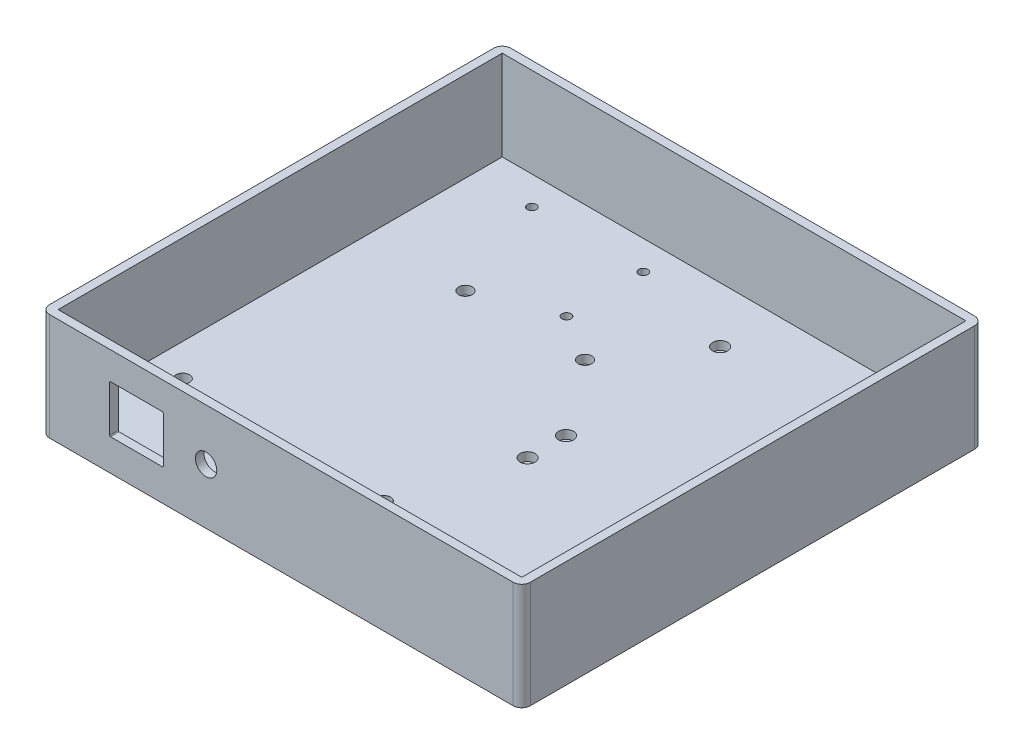
SolidWorks part; units mm, degrees
ref_plane "Front Plane" through (0, 0, 0) normal (0, 0, 1) x (1, 0, 0)
ref_plane "Top Plane" through (0, 0, 0) normal (0, 1, 0) x (1, 0, 0)
ref_plane "Right Plane" through (0, 0, 0) normal (1, 0, 0) x (0, 0, -1)
sketch "Sketch1" plane through (0, 878.6284, 0) normal (0, 1, 0) x (1, 0, 0)
  line L0 (666.5112, -1261.621) -> (666.5112, -1327.661) construction
  line L1 (661.5112, -1230.231) -> (769.8512, -1230.231)
  line L2 (661.5112, -1230.231) -> (661.5112, -1334.011)
  line L3 (661.5112, -1334.011) -> (769.8512, -1334.011)
  line L4 (769.8512, -1230.231) -> (769.8512, -1334.011)
  line L5 (666.5112, -1261.621) -> (666.5112, -1327.661)
  line L6 (666.5112, -1327.661) -> (719.8512, -1327.661) construction
  line L7 (666.5112, -1327.661) -> (719.8512, -1327.661)
  line L8 (764.8512, -1327.661) -> (764.8512, -1284.661) construction
  line L9 (708.6548, -1235.231) -> (672.3548, -1235.231) construction
  line L10 (687.3912, -1334.011) -> (676.2712, -1334.011) construction
  point P4 (643.8312, -1613.7826)
  dimension "D2" = 5
  dimension "D1" = 5
  dimension "D3" = 5
extrude "Boss-Extrude1" add sketch "Sketch1" against normal blind 4 contours L3 L4 L1 L2
sketch "Sketch2" plane through (0, 874.6284, 0) normal (0, 1, 0) x (1, 0, 0)
  line L1 (661.5112, -1230.231) -> (659.5112, -1230.231)
  line L2 (661.5112, -1230.231) -> (661.5112, -1334.011)
  line L3 (661.5112, -1334.011) -> (659.5112, -1334.011)
  line L4 (661.5112, -1230.231) -> (661.5112, -1334.011)
  line L5 (661.5112, -1334.011) -> (769.8512, -1334.011)
  line L6 (769.8512, -1334.011) -> (769.8512, -1230.231)
  line L7 (769.8512, -1230.231) -> (661.5112, -1230.231)
  line L8 (661.5112, -1230.231) -> (661.5112, -1334.011)
  line L9 (661.5112, -1334.011) -> (769.8512, -1334.011)
  line L10 (769.8512, -1334.011) -> (769.8512, -1230.231)
  line L11 (769.8512, -1230.231) -> (661.5112, -1230.231)
  line L12 (659.5112, -1230.231) -> (659.5112, -1334.011)
  line L13 (659.5112, -1230.231) -> (769.8512, -1230.231)
  line L14 (659.5112, -1230.231) -> (659.5112, -1228.231)
  line L15 (659.5112, -1228.231) -> (769.8512, -1228.231)
  line L16 (769.8512, -1230.231) -> (769.8512, -1228.231)
  line L17 (769.8512, -1228.231) -> (771.8512, -1228.231)
  line L18 (769.8512, -1228.231) -> (769.8512, -1334.011)
  line L19 (769.8512, -1334.011) -> (771.8512, -1334.011)
  line L20 (771.8512, -1228.231) -> (771.8512, -1334.011)
  line L21 (659.5112, -1334.011) -> (771.8512, -1334.011)
  line L22 (659.5112, -1334.011) -> (659.5112, -1336.011)
  line L23 (659.5112, -1336.011) -> (771.8512, -1336.011)
  line L24 (771.8512, -1334.011) -> (771.8512, -1336.011)
  dimension "D2" = 2
extrude "Boss-Extrude2" add sketch "Sketch2" along normal blind 25 separate body contours L16 L15 L14 L1 | L1 L12 L3 | L20 L17 L16 L19 | L24 L19 L3 L22 L23 region at (660.5112, 874.6284, 1282.121) region at (714.6812, 874.6284, 1229.231) region at (715.6812, 874.6284, 1335.011) region at (770.8512, 874.6284, 1281.121)
sketch "Sketch4" plane through (0, 0, 1336.011) normal (0, 0, 1) x (1, 0, 0)
  line L0 (687.8912, 893.1684) -> (675.7712, 893.1684)
  line L1 (675.5712, 892.9684) -> (675.5712, 882.2184)
  line L2 (675.7712, 882.0184) -> (687.8912, 882.0184)
  line L3 (688.0912, 882.2184) -> (688.0912, 892.9684)
  line L4 (687.3912, 892.4684) -> (676.2712, 892.4684)
  line L5 (676.2712, 892.4684) -> (676.2712, 882.7184)
  line L6 (676.2712, 882.7184) -> (687.3912, 882.7184)
  line L7 (687.3912, 882.7184) -> (687.3912, 892.4684)
  line L8 (687.3912, 892.4684) -> (676.2712, 892.4684)
  line L9 (676.2712, 892.4684) -> (676.2712, 882.7184)
  line L10 (676.2712, 882.7184) -> (687.3912, 882.7184)
  line L11 (687.3912, 882.7184) -> (687.3912, 892.4684)
  line L12 (675.5712, 882.0184) -> (688.0912, 882.0184) construction
  line L13 (675.5712, 893.1684) -> (675.5712, 882.0184) construction
  line L14 (688.0912, 882.0184) -> (688.0912, 893.1684) construction
  line L15 (688.0912, 893.1684) -> (675.5712, 893.1684) construction
  arc A0 (675.7712, 882.0184) -> (675.5712, 882.2184) centre (675.7712, 882.2184) cw
  arc A1 (688.0912, 882.2184) -> (687.8912, 882.0184) centre (687.8912, 882.2184) cw
  arc A2 (688.0912, 892.9684) -> (687.8912, 893.1684) centre (687.8912, 892.9684) ccw
  arc A3 (675.7712, 893.1684) -> (675.5712, 892.9684) centre (675.7712, 892.9684) ccw
  dimension "D2" = 0.7
extrude "Cut-Extrude1" cut sketch "Sketch4" against normal up to surface (2 mm away) contours L10 L11 L8 L9 | L0 A3 L1 A0 L2 A1 L3 A2 L11 L10 L9 L8 region at (687.9141, 892.9913, 1336.011) region at (681.8312, 887.5934, 1336.011) up to face at (715.6812, 887.1284, 1334.011)
fillet "Fillet1" radius 2 4 edges at (659.5112, 887.1284, 1336.011) (659.5112, 887.1284, 1228.231) (771.8512, 887.1284, 1228.231) (771.8512, 887.1284, 1336.011)
sketch "Sketch5" plane through (0, 878.6284, 0) normal (0, 1, 0) x (1, 0, 0)
  circle A0 centre (761.3512, -1243.161) radius 1.75 construction
  circle A1 centre (761.3512, -1279.161) radius 1.75 construction
  circle A2 centre (725.3512, -1279.161) radius 1.75 construction
  circle A3 centre (725.3512, -1243.161) radius 1.75 construction
  circle A4 centre (761.3512, -1324.161) radius 1.75 construction
  circle A5 centre (761.3512, -1288.161) radius 1.75 construction
  circle A6 centre (725.3512, -1288.161) radius 1.75 construction
  circle A7 centre (725.3512, -1324.161) radius 1.75 construction
  circle A8 centre (669.0512, -1312.421) radius 1.5875 construction
  circle A9 centre (717.3112, -1313.691) radius 1.5875 construction
  circle A10 centre (675.1048, -1236.911) radius 1.05 construction
  circle A11 centre (701.2648, -1237.031) radius 1.05 construction
  circle A12 centre (701.2648, -1254.971) radius 1.05 construction
  circle A13 centre (712.2312, -1261.621) radius 1.5875 construction
  circle A14 centre (684.2912, -1261.621) radius 1.5875 construction
  circle A15 centre (761.3512, -1243.161) radius 1.75
  circle A16 centre (761.3512, -1279.161) radius 1.75
  circle A17 centre (725.3512, -1279.161) radius 1.75
  circle A18 centre (725.3512, -1243.161) radius 1.75
  circle A19 centre (761.3512, -1324.161) radius 1.75
  circle A20 centre (761.3512, -1288.161) radius 1.75
  circle A21 centre (725.3512, -1288.161) radius 1.75
  circle A22 centre (725.3512, -1324.161) radius 1.75
  circle A23 centre (669.0512, -1312.421) radius 1.5875
  circle A24 centre (717.3112, -1313.691) radius 1.5875
  circle A25 centre (675.1048, -1236.911) radius 1.05
  circle A26 centre (701.2648, -1237.031) radius 1.05
  circle A27 centre (701.2648, -1254.971) radius 1.05
  circle A28 centre (712.2312, -1261.621) radius 1.5875
  circle A29 centre (684.2912, -1261.621) radius 1.5875
extrude "Cut-Extrude2" cut sketch "Sketch5" against normal blind 2
sketch "Sketch6" plane through (0, 0, 1336.011) normal (0, 0, 1) x (1, 0, 0)
  line L0 (698.0912, 887.5934) -> (688.0912, 887.5934)
  line L1 (688.0912, 882.2184) -> (688.0912, 892.9684) construction
  circle A0 centre (698.0912, 887.5934) radius 2.5
  dimension "D1" = 5
  dimension "D2" = 10
extrude "Cut-Extrude3" cut sketch "Sketch6" against normal up to surface (2 mm away) contours A0 region at (698.0912, 885.1641, 1336.011) up to face at (681.8312, 887.5934, 1334.011)
equation "\"D2\"=110"
equation "\"C\"=5"
equation "\"D2@Sketch1\"=\"C\""
equation "\"D1\"=100"
equation "\"T\"= 2"
equation "\"BT\"=4"
equation "\"D1@Boss-Extrude1\"=\"BT\""
equation "\"D1@Sketch1\"=\"C\""
equation "\"D3@Sketch1\"=\"C\""
equation "\"D2@Sketch2\"=\"T\""
equation "\"H\"= 25"
equation "\"D1@Boss-Extrude2\"=\"H\""
equation "\"CS\"=0.7"
equation "\"D2@Sketch4\"=\"CS\""
equation "\"F\"=0.2"
equation "\"D3@Sketch4\"=\"F\""
equation "\"F2\"=2"
equation "\"D1@Fillet1\"=\"F2\""
equation "\"D\"=2"
equation "\"D1@Cut-Extrude2\"=\"D\""
equation "\"HOLED\"=5"
equation "\"D1@Sketch6\"=\"HOLED\""
